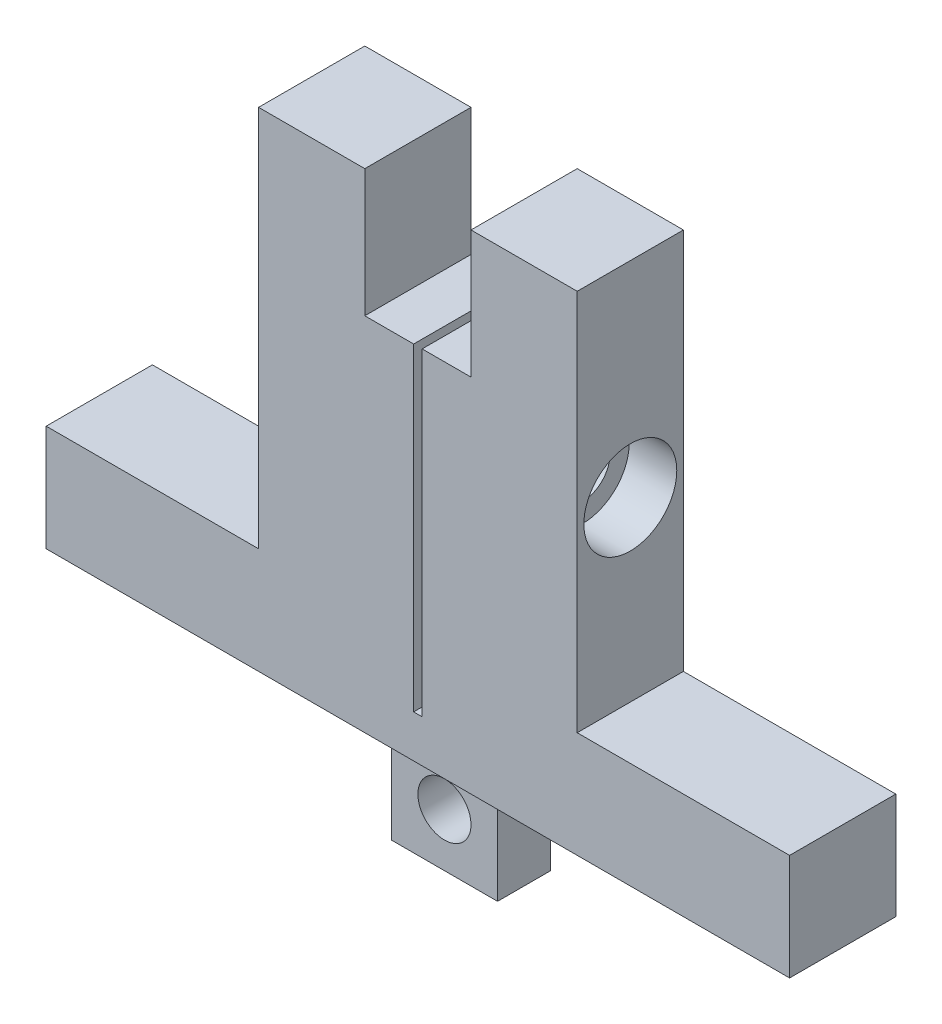
SolidWorks part; units mm, degrees
material "6061 Alloy"
ref_plane "Front Plane" through (0, 0, 0) normal (0, 0, 1) x (1, 0, 0)
ref_plane "Top Plane" through (0, 0, 0) normal (0, 1, 0) x (1, 0, 0)
ref_plane "Right Plane" through (0, 0, 0) normal (1, 0, 0) x (0, 0, -1)
sketch "Sketch2" plane through (0, 0, 0) normal (0, 0, 1) x (1, 0, 0)
  line L1 (-9.525, -15.875) -> (9.525, -15.875)
  line L2 (-9.525, -15.875) -> (-9.525, 15.875)
  line L3 (-9.525, 15.875) -> (9.525, 15.875)
  line L4 (9.525, -15.875) -> (9.525, 15.875)
  line L5 (-9.525, -15.875) -> (9.525, 15.875) construction
  line L6 (-9.525, 15.875) -> (9.525, -15.875) construction
  point P0 (0, 0)
  dimension "D1" = 31.75
  dimension "D2" = 19.05
extrude "Boss-Extrude1" add sketch "Sketch2" along normal mid plane 6.35
sketch "Sketch4" plane through (-1.5069, 3.1105, 3.175) normal (0, 0, 1) x (1, 0, 0)
  line L1 (-1.6681, 12.7645) -> (4.6819, 12.7645)
  line L2 (-1.6681, 12.7645) -> (-1.6681, 2.6045)
  line L3 (-1.6681, 2.6045) -> (4.6819, 2.6045)
  line L4 (4.6819, 12.7645) -> (4.6819, 2.6045)
  line L7 (-8.0181, 12.7645) -> (11.0319, 12.7645)
  line L8 (-8.0181, 12.7645) -> (-8.0181, 10.2245)
  line L9 (-8.0181, 10.2245) -> (11.0319, 10.2245)
  line L10 (11.0319, 12.7645) -> (11.0319, 10.2245)
  line L11 (11.0319, 12.7645) -> (-8.0181, 12.7645) construction
  line L12 (11.0319, -18.9855) -> (11.0319, 12.7645) construction
  line L13 (-8.0181, 12.7645) -> (-8.0181, -18.9855) construction
  dimension "D1" = 6.35
  dimension "D2" = 0
  dimension "D3" = 10.16
  dimension "D4" = 2.54
  dimension "D5" = 0
  dimension "D6" = 0
  dimension "D7" = 0
  dimension "D8" = 6.35
extrude "Cut-Extrude1" cut sketch "Sketch4" against normal through all contours L4 L9 | L2 L9 L4 | L9 L2 L3 L4 | L9 L2 region at (0, 14.605, 3.175) region at (-6.35, 14.605, 3.175) region at (6.35, 14.605, 3.175) region at (0, 9.525, 3.175)
sketch "Sketch20" plane through (0, 0, 3.175) normal (0, 0, 1) x (1, 0, 0)
  line L1 (9.525, -15.875) -> (22.225, -15.875)
  line L2 (9.525, -15.875) -> (9.525, -9.525)
  line L3 (9.525, -9.525) -> (22.225, -9.525)
  line L4 (22.225, -15.875) -> (22.225, -9.525)
  dimension "D1" = 12.7
  dimension "D2" = 6.35
extrude "Boss-Extrude2" add sketch "Sketch20" against normal through all
mirror "Mirror1" about plane through (0, 0, 0) normal (1, 0, 0) of "Boss-Extrude2"
sketch "Sketch21" plane through (0, 0, -3.175) normal (0, 0, -1) x (-1, 0, 0)
  line L0 (22.225, -15.875) -> (-22.225, -15.875) construction
  line L1 (-3.175, -9.525) -> (3.175, -9.525)
  line L2 (-3.175, -9.525) -> (-3.175, -22.225)
  line L3 (-3.175, -22.225) -> (3.175, -22.225)
  line L4 (3.175, -9.525) -> (3.175, -22.225)
  line L5 (-3.175, -9.525) -> (3.175, -22.225) construction
  line L6 (-3.175, -22.225) -> (3.175, -9.525) construction
  point P0 (0, -15.875)
  dimension "D1" = 6.35
  dimension "D2" = 6.35
extrude "Boss-Extrude4" add sketch "Sketch21" against normal blind 3.175 from offset 1.5875 offset against normal yes
sketch "Sketch22" plane through (0, 0, -3.175) normal (0, 0, -1) x (-1, 0, 0)
  line L0 (-3.175, -22.225) -> (3.175, -22.225) construction
  line L1 (-3.175, -15.875) -> (-3.175, -22.225) construction
  circle A0 centre (0, -19.05) radius 1.5875
  dimension "D3" = 3.175
  dimension "D1" = 3.175
  dimension "D2" = 3.175
extrude "Cut-Extrude3" cut sketch "Sketch22" against normal through all
sketch "Sketch23" plane through (0, 0, 3.175) normal (0, 0, 1) x (1, 0, 0)
  line L0 (-3.175, 5.715) -> (3.175, 5.715) construction
  line L1 (-0.254, 5.715) -> (0.254, 5.715)
  line L2 (-0.254, 5.715) -> (-0.254, -13.335)
  line L3 (-0.254, -13.335) -> (0.254, -13.335)
  line L4 (0.254, 5.715) -> (0.254, -13.335)
  line L5 (-0.254, 5.715) -> (0.254, -13.335) construction
  line L6 (-0.254, -13.335) -> (0.254, 5.715) construction
  point P0 (0, -3.81)
  dimension "D1" = 0.508
  dimension "D2" = 0
  dimension "D3" = 19.05
  dimension "D4" = 0
extrude "Cut-Extrude4" cut sketch "Sketch23" against normal through all
hole_wizard "CBORE for #4 Socket Head Cap Screw1" positions "Sketch25" profile "Sketch26" counterbore size "#4" standard "ANSI Inch" end condition up to next
sketch "Sketch25" plane through (9.525, 0, 0) normal (1, 0, 0) x (0, 0, -1)
  point P0 (0, 1.075)
sketch "Sketch26" plane through (9.525, 1.075, 0) normal (0, 1, 0) x (0, 0, -1)
  line L0 (0, 0) -> (0, 9.271)
  line L1 (0, 9.271) -> (1.6319, 9.271)
  line L3 (1.6319, 9.271) -> (1.6319, 2.8448)
  line L4 (1.6319, 2.8448) -> (2.7788, 2.8448)
  line L5 (2.7788, 2.8448) -> (2.7788, 0)
  line L7 (2.7788, 0) -> (0, 0)
  line L11 (0, -6.35) -> (0, 107.95) construction
  dimension "Thru Hole Dia." = 3.2639
  dimension "Thru Hole Depth" = 9.271
  dimension "C'Bore Dia." = 5.5575
  dimension "C'Bore Depth" = 2.8448
hole_wizard "#4-40 Tapped Hole1" positions "Sketch27" profile "Sketch28" tap size "#4-40" standard "ANSI Inch" end condition through all
sketch "Sketch27" plane through (-0.254, 0, 0) normal (1, 0, 0) x (0, 0, -1)
  point P0 (0, 1.075)
sketch "Sketch28" plane through (-0.254, 1.075, 0) normal (0, 1, 0) x (0, 0, -1)
  line L0 (0, 0) -> (0, 21.971)
  line L1 (0, 21.971) -> (1.1303, 21.971)
  line L2 (1.1303, 21.971) -> (1.1303, 0)
  line L5 (1.1303, 0) -> (0, 0)
  line L11 (0, -6.35) -> (0, 107.95) construction
  dimension "Thru Tap Drill Dia." = 2.2606
  dimension "Thru Tap Drill Depth" = 21.971
cosmetic thread "Hole Thread1" parameters "D2"=2.8448
